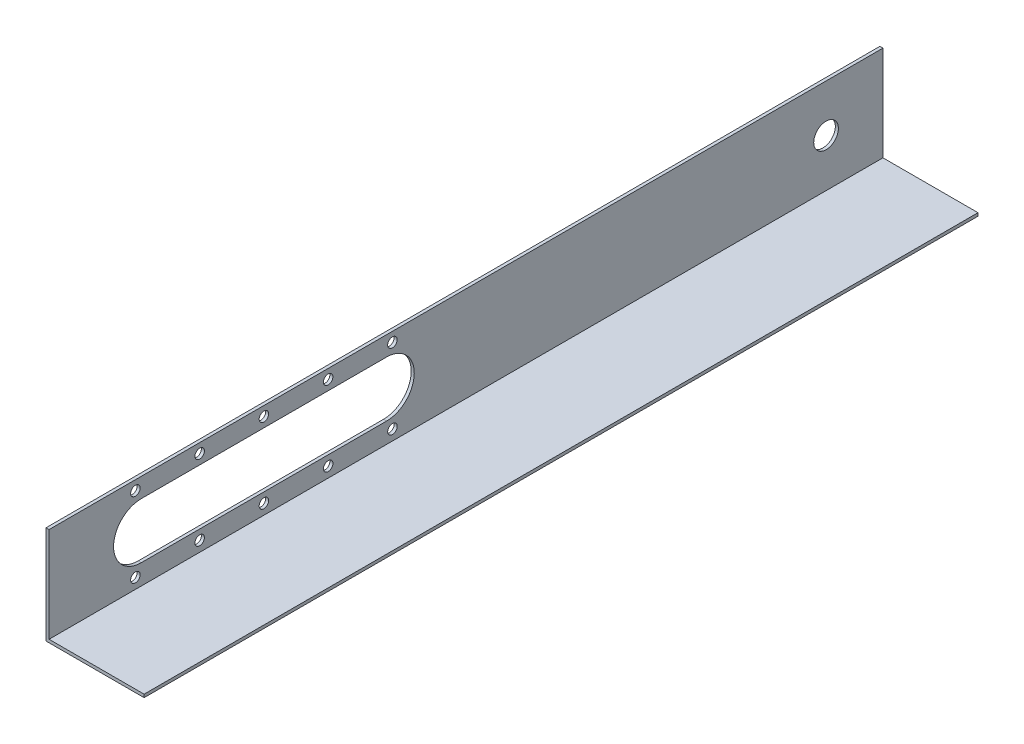
SolidWorks part; units mm, degrees
ref_plane "Front Plane" through (0, 0, 0) normal (0, 0, 1) x (1, 0, 0)
ref_plane "Top Plane" through (0, 0, 0) normal (0, 1, 0) x (1, 0, 0)
ref_plane "Right Plane" through (0, 0, 0) normal (1, 0, 0) x (0, 0, -1)
sketch "Sketch3" plane through (0, 0, 0) normal (0, 0, 1) x (1, 0, 0)
  line L0 (0, 0) -> (0, 49.2125)
  line L1 (0, 49.2125) -> (-1.5875, 49.2125)
  line L2 (-1.5875, 49.2125) -> (-1.5875, -1.5875)
  line L3 (-1.5875, -1.5875) -> (49.2125, -1.5875)
  line L4 (49.2125, -1.5875) -> (49.2125, 0)
  line L5 (49.2125, 0) -> (0, 0)
  dimension "D1" = 1.5875
  dimension "D2" = 1.5875
  dimension "D3" = 50.8
  dimension "D4" = 50.8
extrude "Boss-Extrude2" add sketch "Sketch3" along normal blind 431.8
sketch "Sketch6" plane through (0, 0, 0) normal (1, 0, 0) x (0, 0, -1)
  line L0 (-384.048, 24.8285) -> (-257.048, 24.8285) construction
  line L1 (-384.048, 39.1795) -> (-257.048, 39.1795)
  line L2 (-384.048, 10.4775) -> (-257.048, 10.4775)
  line L3 (-431.8, 0) -> (-431.8, 49.2125) construction
  line L5 (-431.8, 49.2125) -> (0, 49.2125) construction
  arc A0 (-384.048, 39.1795) -> (-384.048, 10.4775) centre (-384.048, 24.8285) ccw
  arc A1 (-257.048, 10.4775) -> (-257.048, 39.1795) centre (-257.048, 24.8285) ccw
  point P2 (-320.548, 24.8285)
  dimension "D3" = 47.752
  dimension "D1" = 28.702
  dimension "D2" = 127
  dimension "D4" = 24.384
extrude "Cut-Extrude3" cut sketch "Sketch6" against normal blind 127
sketch "Sketch7" plane through (0, 0, 0) normal (1, 0, 0) x (0, 0, -1)
  line L1 (-431.8, 49.2125) -> (0, 49.2125) construction
  line L2 (0, 0) -> (0, 49.2125) construction
  circle A0 centre (-29.464, 24.7736) radius 6.3881
  dimension "D1" = 12.7762
  dimension "D3" = 24.4389
  dimension "D2" = 29.464
extrude "Cut-Extrude4" cut sketch "Sketch7" against normal through all
sketch "Sketch12" plane through (0, 0, 0) normal (1, 0, 0) x (0, 0, -1)
  line L0 (-257.048, 39.1795) -> (-384.048, 39.1795) construction
  line L1 (-384.048, 10.4775) -> (-257.048, 10.4775) construction
  arc A0 (-384.048, 39.1795) -> (-384.048, 10.4775) centre (-384.048, 24.8285) ccw construction
  point P0 (-320.548, 44.2595)
  point P1 (-254, 44.2595)
  point P4 (-320.548, 39.1795)
  point P6 (-320.548, 5.3975)
  point P7 (-254, 44.2595)
  point P8 (-254, 5.3975)
  point P10 (-254, 5.3975)
  point P12 (-287.274, 44.2595)
  point P13 (-287.274, 44.2595)
  point P14 (-287.274, 5.3975)
  point P15 (-287.274, 5.3975)
  point P16 (-353.822, 44.2595)
  point P17 (-387.096, 44.2595)
  point P18 (-387.096, 5.3975)
  point P21 (-353.822, 5.3975)
  dimension "D1" = 5.08
  dimension "D2" = 63.5
  dimension "D3" = 33.274
  dimension "D4" = 33.274
  dimension "D5" = 33.274
  dimension "D6" = 33.274
  dimension "D7" = 63.5
  dimension "D8" = 5.08
  dimension "D9" = 33.274
  dimension "D10" = 33.274
  dimension "D11" = 33.274
  dimension "D12" = 33.274
  dimension "D13" = 33.274
  dimension "D14" = 33.274
  dimension "D15" = 33.274
  dimension "D16" = 33.274
hole_wizard "#10 (0.1935) Diameter Hole3" positions "Sketch13" profile "Sketch14" hole size "#10" standard "ANSI Inch" end condition through all
sketch "Sketch13" plane through (0, 0, 0) normal (1, 0, 0) x (0, 0, -1)
  point P0 (-254, 44.2595)
  point P3 (-287.274, 44.2595)
  point P6 (-320.548, 44.2595)
  point P9 (-287.274, 44.2595)
  point P12 (-254, 44.2595)
  point P15 (-254, 5.3975)
  point P18 (-287.274, 5.3975)
  point P21 (-320.548, 5.3975)
  point P24 (-287.274, 5.3975)
  point P27 (-254, 5.3975)
  point P30 (-353.822, 44.2595)
  point P33 (-387.096, 44.2595)
  point P36 (-387.096, 5.3975)
  point P39 (-353.822, 5.3975)
sketch "Sketch14" plane through (0, 44.2595, 254) normal (0, 1, 0) x (0, 0, -1)
  line L0 (0, 0) -> (0, 1.5875)
  line L1 (0, 1.5875) -> (2.4574, 1.5875)
  line L2 (2.4574, 1.5875) -> (2.4574, 0)
  line L5 (2.4574, 0) -> (0, 0)
  line L11 (0, -6.35) -> (0, 107.95) construction
  dimension "Thru Hole Dia." = 4.9149
  dimension "Thru Hole Depth" = 1.5875
